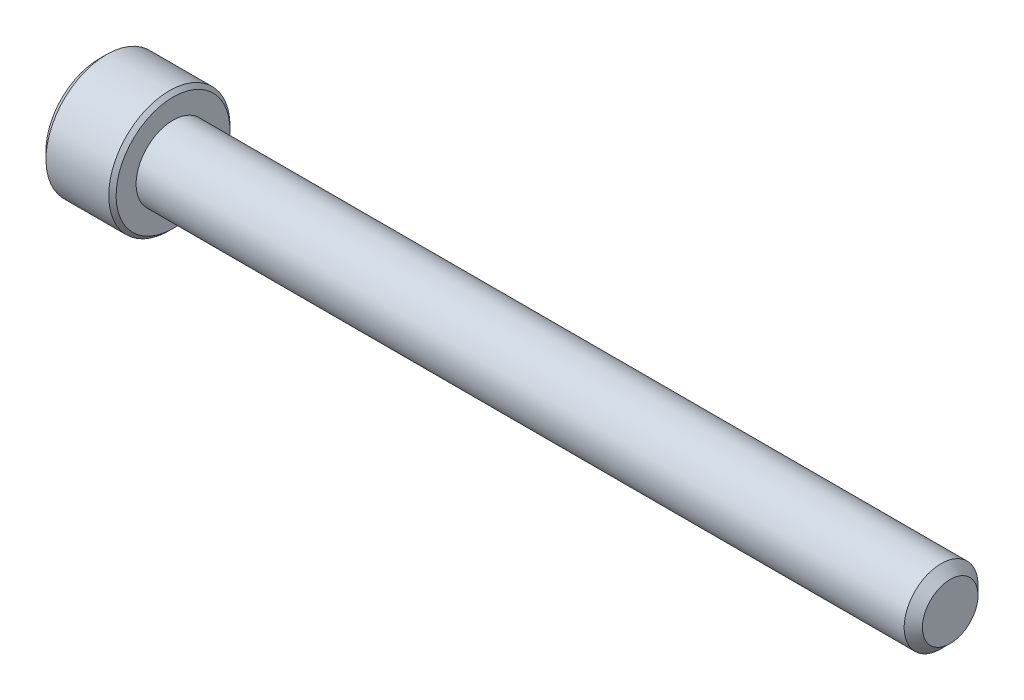
SolidWorks part; units mm, degrees
material "Plain Carbon Steel"
ref_plane "Front Plane" through (0, 0, 0) normal (0, 0, 1) x (1, 0, 0)
ref_plane "Top Plane" through (0, 0, 0) normal (0, 1, 0) x (1, 0, 0)
ref_plane "Right Plane" through (0, 0, 0) normal (1, 0, 0) x (0, 0, -1)
sketch "Sketch1" plane through (0, 0, 0) normal (0, 0, 1) x (1, 0, 0)
  line L0 (25.4, 0) -> (-25.4, 0) construction
  line L1 (25.4, 2.413) -> (25.4, -2.413) construction
  line L2 (-25.4, 3.7211) -> (-25.4, -3.7211) construction
  line L3 (-25.6413, 3.9624) -> (-29.7434, 3.9624) construction
  line L4 (-29.7434, 3.9624) -> (-30.226, 3.4798) construction
  line L5 (-30.226, 3.4798) -> (-30.226, -3.4798) construction
  line L6 (-30.226, -3.4798) -> (-29.7434, -3.9624) construction
  line L7 (-29.7434, -3.9624) -> (-25.6413, -3.9624) construction
  line L8 (-25.6413, 3.9624) -> (-25.4, 3.7211) construction
  line L9 (-25.4, -3.7211) -> (-25.6413, -3.9624) construction
  point P5 (-25.4, 3.9624)
  point P6 (-25.4, -3.9624)
  point P7 (-27.94, 0)
  point P12 (22.225, -2.413)
  dimension "D1" = 45
  dimension "Dec." = 4.826
  dimension "Length" = 50.8
  dimension "Head Dia" = 7.9248
  dimension "Head Height" = 4.826
  dimension "Hex Depth" = 2.286
  dimension "Chamfer" = 0.4826
  dimension "D2" = 3.175
  dimension "D3" = 0.2413
  dimension "D4" = 45
ref_plane "Plane1" through (25.4, 0, 0) normal (1, 0, 0) x (0, 0, -1)
ref_plane "Plane2" through (-30.226, 0, 0) normal (1, 0, 0) x (0, 0, -1)
sketch "Sketch2" plane through (25.4, 0, 0) normal (1, 0, 0) x (0, 0, -1)
  circle A0 centre (0, 0) radius 2.413
extrude "Boss-Extrude1" add sketch "Sketch2" against normal up to vertex (50.8 mm away) up to point (-25.4, 0, 0)
sketch "Sketch3" plane through (25.4, 0, 0) normal (1, 0, 0) x (0, 0, -1)
  circle A0 centre (0, 0) radius 2.413 construction
  circle A1 centre (0, 0) radius 2.413
curve "Helix/Spiral1" pitch 0.7937 height 51.5938 turns 65 parameters "Pitch"=0.7937
chamfer "Chamfer1" distance 0.5953 angle 45 1 edges at (25.4, 0, -2.413)
sketch "Sketch5" plane through (0, 0, 0) normal (0, 0, 1) x (1, 0, 0)
  line L0 (25.0527, 2.413) -> (25.7473, 2.413)
  line L1 (25.7473, 2.413) -> (25.4496, 1.8974)
  line L2 (25.4496, 1.8974) -> (25.3504, 1.8974)
  line L3 (25.3504, 1.8974) -> (25.0527, 2.413)
  line L4 (25.4, 1.8974) -> (25.4, 2.413) construction
  line L5 (25.2016, 2.1552) -> (25.5984, 2.1552) construction
  dimension "D1" = 60
  dimension "D2" = 0.3969
  dimension "D3" = 0.0992
sweep "Cut-Sweep1" [suppressed] cut profiles "Sketch5" path "Helix/Spiral1"
sketch "Sketch4" plane through (-30.226, 0, 0) normal (1, 0, 0) x (0, 0, -1)
  line L0 (-3.9624, 0.7937) -> (3.9624, 0.7937) construction
  line L1 (0, 2.2877) -> (-1.9812, 1.1438)
  line L2 (-1.9812, 1.1438) -> (-1.9812, -1.1438)
  line L3 (-1.9812, -1.1438) -> (0, -2.2877)
  line L4 (0, -2.2877) -> (1.9812, -1.1438)
  line L5 (1.9812, -1.1438) -> (1.9812, 1.1438)
  line L6 (1.9812, 1.1438) -> (0, 2.2877)
  line L7 (0, 0) -> (0, 0.7937) construction
  circle A0 centre (0, 0) radius 1.9812 construction
  dimension "Hex Size" = 3.9624
  dimension "D1" = 7.9248
  dimension "D2" = 0.7937
sketch "Sketch6" plane through (0, 0, 0) normal (0, 0, 1) x (1, 0, 0)
  line L0 (-29.7434, 3.9624) -> (-30.226, 3.4798) construction
  line L2 (-25.4, 3.7211) -> (-25.4, -3.7211) construction
  line L3 (-30.226, 3.4798) -> (-30.226, -3.4798) construction
  line L4 (-29.7434, 3.9624) -> (-30.226, 3.4798)
  line L5 (-25.6413, 3.9624) -> (-29.7434, 3.9624) construction
  line L6 (-25.4, 3.7211) -> (-25.4, 0)
  line L7 (-30.226, 3.4798) -> (-30.226, 0)
  line L8 (-25.4, 0) -> (-30.226, 0) construction
  line L9 (-25.4, 0) -> (-30.226, 0)
  line L10 (-25.6413, 3.9624) -> (-25.4, 3.7211) construction
  line L11 (-25.6413, 3.9624) -> (-29.7434, 3.9624)
  line L12 (-25.6413, 3.9624) -> (-25.4, 3.7211)
revolve "Revolve1" add sketch "Sketch6" angle 360 about L8
extrude "Cut-Extrude1" cut sketch "Sketch4" along normal up to vertex (2.286 mm away) up to point (-27.94, 0, 0)
sketch "Sketch8" plane through (-30.226, 0, 0) normal (-1, 0, 0) x (0, 0, 1)
  circle A1 centre (0, 0) radius 2.2877
extrude "Cut-Extrude2" cut sketch "Sketch8" against normal blind 0.9652 draft 45
equation "\"D3@Helix/Spiral1\" = \"Length@Sketch1\"+\"Pitch@Helix/Spiral1\""
equation "\"D3@Sketch5\" = \"Pitch@Helix/Spiral1\"*.125"
equation "\"D2@Sketch5\" = \"Pitch@Helix/Spiral1\"*.50"
equation "\"D1@Chamfer1\" = \"Pitch@Helix/Spiral1\"*.75"
equation "\"D2@Sketch1\" = \"Pitch@Helix/Spiral1\"*4"
equation "\"D1@Sketch4\" = \"Head Dia@Sketch1\""
equation "\"Chamfer@Sketch1\" = \"Head Height@Sketch1\"/10"
equation "\"D3@Sketch1\" = \"Chamfer@Sketch1\"/2"
equation "\"D1@Cut-Extrude2\" = \"Chamfer@Sketch1\"*2"
